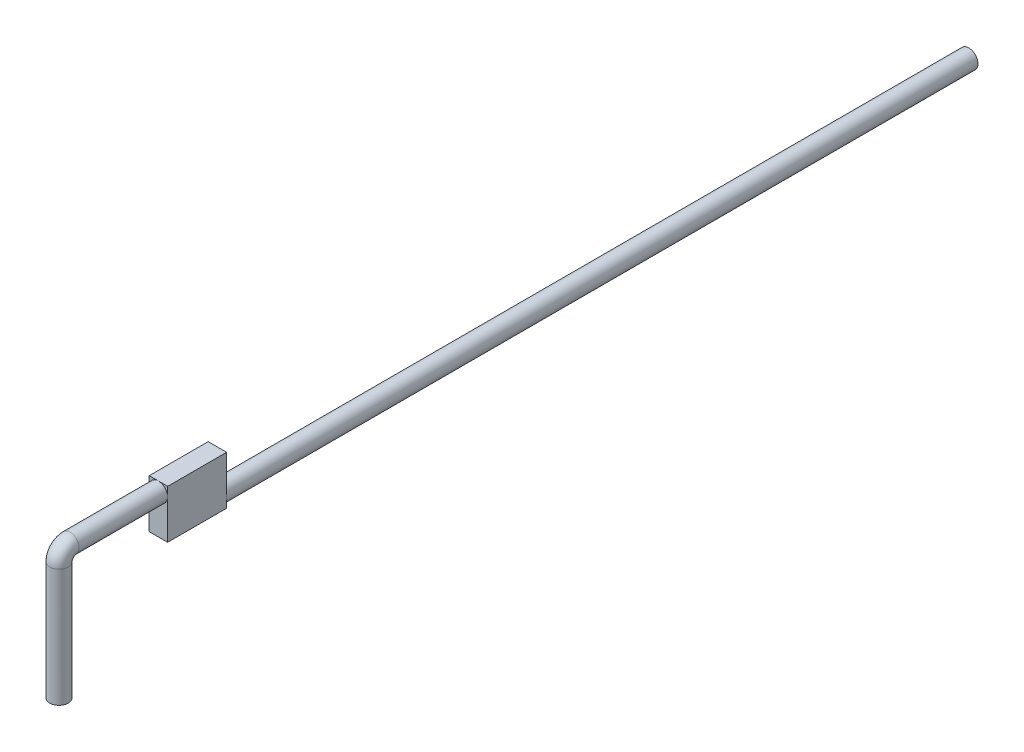
SolidWorks part; units mm, degrees
ref_plane "Front Plane" through (0, 0, 0) normal (0, 0, 1) x (1, 0, 0)
ref_plane "Top Plane" through (0, 0, 0) normal (0, 1, 0) x (1, 0, 0)
ref_plane "Right Plane" through (0, 0, 0) normal (1, 0, 0) x (0, 0, -1)
sketch "Sketch1" plane through (0, 0, 0) normal (0, 0, 1) x (1, 0, 0)
  circle A0 centre (0, 0) radius 1.9844
  dimension "D1" = 3.9688
extrude "Boss-Extrude1" add sketch "Sketch1" along normal blind 168.275
sketch "Sketch2" plane through (0, 0, 168.275) normal (0, 0, 1) x (1, 0, 0)
  line L1 (-1.9844, -1.9844) -> (1.9844, -1.9844)
  line L2 (-1.9844, -1.9844) -> (-1.9844, 8.4713)
  line L3 (-1.9844, 8.4713) -> (1.9844, 8.4713)
  line L4 (1.9844, -1.9844) -> (1.9844, 8.4713)
  circle A0 centre (0, 0) radius 1.9844 construction
extrude "Boss-Extrude2" add sketch "Sketch2" along normal blind 6.35 and the other way blind 6.35
sketch "Sketch3" plane through (0, 0, 174.625) normal (0, 0, 1) x (1, 0, 0)
  line L0 (1.9844, 8.4713) -> (-1.9844, 8.4713) construction
  circle A0 centre (0, 6.4869) radius 1.9844
  dimension "D1" = 3.9688
extrude "Boss-Extrude3" add sketch "Sketch3" along normal blind 19.05
sketch "Sketch4" plane through (0, 0, 193.675) normal (0, 0, 1) x (1, 0, 0)
  circle A0 centre (0, 6.4869) radius 1.9844
sketch "Sketch5" plane through (0, 0, 193.675) normal (0, 0, 1) x (1, 0, 0)
  line L0 (-5.9723, 4.113) -> (7.0862, 4.113) construction
revolve "Revolve5" add sketch "Sketch4" angle 90 about L0
sketch "Sketch6" plane through (0, 4.113, 0) normal (0, -1, 0) x (1, 0, 0)
  circle A0 centre (0, 196.0489) radius 1.9844
extrude "Boss-Extrude4" add sketch "Sketch6" along normal blind 25.4
